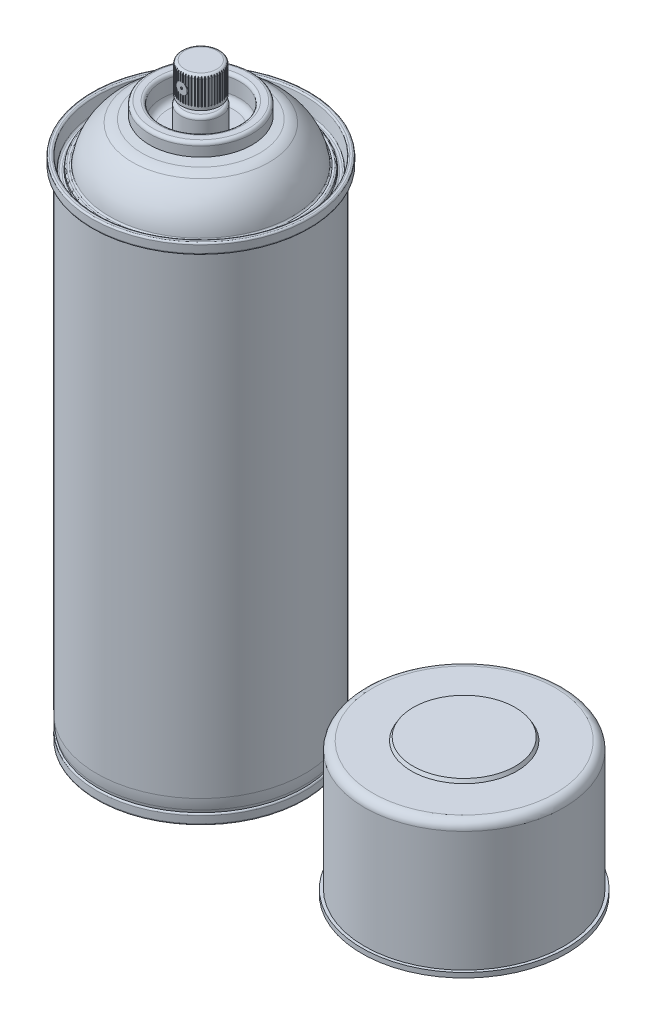
SolidWorks part; units mm, degrees
ref_plane "Front Plane" through (0, 0, 0) normal (0, 0, 1) x (1, 0, 0)
ref_plane "Top Plane" through (0, 0, 0) normal (0, 1, 0) x (1, 0, 0)
ref_plane "Right Plane" through (0, 0, 0) normal (1, 0, 0) x (0, 0, -1)
sketch "Sketch1" plane through (0, 0, 0) normal (0, 1, 0) x (1, 0, 0)
  circle A0 centre (0, 0) radius 32.5
  dimension "D1" = 65
extrude "Boss-Extrude1" add sketch "Sketch1" along normal blind 158
sketch "Sketch2" plane through (0, 0, 0) normal (0, -1, 0) x (1, 0, 0)
  circle A1 centre (0, 0) radius 32.5
  circle A2 centre (0, 0) radius 32.5
  dimension "D1" = 0
chamfer "Chamfer1" distance 1 angle 80 1 edges at (0, 0, 32.5) first distance on face at (0, 0, 32.5)
fillet "Fillet1" radius 19 1 edges at (0, 5.6713, 32.5)
other "Move Face1" flip direction yes face at (0, 0, 31.5) offset 2.5 parameters "D1"=2.5
dome "Dome1" faces to dome 1 distance 6 reverse direction yes elliptical dome no face at (0, 2.5, 31.9408) parameters "D1"=6
extrude "Extrude-Thin1" add sketch "Sketch2" against normal blind 3.2 separate body thin thin type one direction reverse wall 1.5
combine bodies "Combine1" operation type add bodies to combine 101 103
fillet "Fillet2" radius 0.5 4 edges at (31, 0, 0) (0, 3.2, -32.5) (0, 0, -32.5) (0, 2.8602, -31)
sketch "Sketch3" plane through (0, 158, 0) normal (0, 1, 0) x (1, 0, 0)
  circle A1 centre (0, 0) radius 32.5
  circle A2 centre (0, 0) radius 32.5
  dimension "D1" = 0
extrude "Cut-Extrude1" cut sketch "Sketch3" against normal blind 3.9
sketch "Sketch4" plane through (0, 0, 0) normal (0, 0, 1) x (1, 0, 0)
  line L0 (0, 146.9302) -> (0, 222.3926) construction
  line L1 (-12.8, 168.6) -> (-19.8, 167.9876)
  line L2 (0, 158.6) -> (-34, 158.6) construction
  line L3 (0, 173.1) -> (-44.1761, 173.1) construction
  line L4 (-34, 158.6) -> (-32.5, 158.6)
  line L5 (-34, 158.6) -> (-34, 155.3)
  line L6 (-34, 155.3) -> (-32.5, 155.3)
  line L7 (-32.5, 155.3) -> (-32.5, 153.1)
  line L8 (-16, 173.1) -> (-16, 220.9613) construction
  line L9 (-12.2, 170.1) -> (-12.2, 172.1)
  line L10 (-13.2, 173.1) -> (-15, 173.1)
  line L11 (-16, 172.1) -> (-16, 169.1)
  line L12 (-6.25, 165.6) -> (-10.2, 165.6)
  line L13 (-6.25, 165.6) -> (-6.25, 172.1)
  line L14 (-16, 169.1) -> (-15.5, 169.1)
  line L15 (-15.5, 169.1) -> (-15.5, 171.6)
  line L16 (-14.5, 172.6) -> (-13.8, 172.6)
  line L17 (-12.2, 170.1) -> (-12.2, 167.6)
  line L18 (-12.8, 171.6) -> (-12.8, 168.6)
  line L19 (-5.25, 173.1) -> (0, 173.1)
  line L20 (-30.2065, 154.1) -> (-31.7065, 154.1)
  line L21 (-31.7065, 154.1) -> (-32.5, 158.6)
  line L22 (-32.5, 153.1) -> (0, 153.1)
  line L23 (0, 153.1) -> (0, 173.1)
  line L24 (32.5, 154.1) -> (-32.5, 154.1) construction
  line L26 (-30.2065, 154.1) -> (-30.0753, 155.6)
  line L27 (-30.0753, 155.6) -> (-28.5753, 155.6)
  arc A0 (-28.5753, 155.6) -> (-19.8, 167.9876) centre (-12.6943, 153.652) cw
  arc A1 (-15, 173.1) -> (-16, 172.1) centre (-15, 172.1) ccw
  arc A2 (-12.2, 172.1) -> (-13.2, 173.1) centre (-13.2, 172.1) ccw
  arc A3 (-12.8, 171.6) -> (-13.8, 172.6) centre (-13.8, 171.6) ccw
  arc A4 (-15.5, 171.6) -> (-14.5, 172.6) centre (-14.5, 171.6) cw
  arc A5 (-6.25, 172.1) -> (-5.25, 173.1) centre (-5.25, 172.1) cw
  arc A6 (-10.2, 165.6) -> (-12.2, 167.6) centre (-10.2, 167.6) cw
  point P35 (-12.2, 173.1)
  point P38 (-12.8, 172.6)
  point P43 (-6.25, 173.1)
  dimension "D15" = 95
  dimension "D20" = 1
  dimension "D21" = 1
  dimension "D22" = 2
  dimension "D27" = 95
  dimension "D29" = 16
  dimension "D2" = 3.3
  dimension "D3" = 1.5
  dimension "D4" = 14.5
  dimension "D5" = 16
  dimension "D6" = 4
  dimension "D7" = 3
  dimension "D8" = 3.8
  dimension "D9" = 7.5
  dimension "D10" = 6.25
  dimension "D11" = 0.5
  dimension "D12" = 0.5
  dimension "D13" = 4
  dimension "D14" = 0.6
  dimension "D16" = 1.5
  dimension "D17" = 100
  dimension "D18" = 1.5
  dimension "D19" = 20
  dimension "D23" = 34
  dimension "D24" = 1.2
  dimension "D25" = 1.5
  dimension "D26" = 1.5
  dimension "D28" = 7
revolve "Revolve1" add sketch "Sketch4" angle 360 about L0
fillet "Fillet4" radius 0.5 4 edges at (0, 154.1, -31.7065) (0, 158.6, -32.5) (0, 155.3, -34) (0, 158.6, -34)
fillet "Fillet6" radius 0.5 3 edges at (0, 155.6, -28.5753) (0, 155.6, -30.0753) (0, 154.1, -30.2065)
fillet "Fillet7" radius 6.5 1 edges at (0, 167.9876, -19.8)
sketch "Sketch5" plane through (0, 0, 0) normal (0, 0, 1) x (1, 0, 0)
  line L0 (-30.5, 157.1) -> (-30.5, 196.1)
  line L1 (-28.5, 198.1) -> (0, 198.1)
  line L2 (5.25, 173.1) -> (-5.25, 173.1) construction
  line L3 (0, 172.1) -> (0, 198.1) construction
  line L4 (16, 172.1) -> (-16, 172.1) construction
  line L5 (-32, 157.1) -> (-30.5, 157.1)
  line L6 (-31.1, 158.6) -> (-31.1, 196.1)
  line L7 (-28.5, 198.7) -> (-16.5, 198.7)
  line L8 (0, 199.7) -> (0, 198.1)
  line L9 (-31.1, 158.6) -> (-32, 158.6)
  line L10 (-32, 158.6) -> (-32, 157.1)
  line L11 (-16.5, 198.7) -> (-15.9226, 199.7)
  line L12 (-15.9226, 199.7) -> (0, 199.7)
  line L13 (-31.1, 157.1) -> (-31.1, 196.1) construction
  line L14 (-28.5, 198.7) -> (0, 198.7) construction
  arc A1 (-30.5, 196.1) -> (-28.5, 198.1) centre (-28.5, 196.1) cw
  arc A2 (-31.1, 196.1) -> (-28.5, 198.7) centre (-28.5, 196.1) cw
  point P13 (-30.5, 198.1)
  dimension "D3" = 2
  dimension "D1" = 16
  dimension "D2" = 41
  dimension "D5" = 1.5
  dimension "D6" = 1.5
  dimension "D7" = 30.5
  dimension "D8" = 16.5
  dimension "D9" = 1
  dimension "D10" = 120
  dimension "D4" = 0.6
revolve "Revolve2" add sketch "Sketch5" angle 360 about L3
sketch "Sketch6" plane through (0, 0, 0) normal (0, 0, 1) x (1, 0, 0)
  line L0 (0, 172.1) -> (0, 184.1)
  line L1 (0, 172.1) -> (0, 198.1) construction
  line L2 (0, 184.1) -> (-6, 184.1)
  line L3 (-6, 184.1) -> (-6, 174.6)
  line L4 (-6, 174.6) -> (-3, 174.6)
  line L5 (-3, 174.6) -> (-3, 172.1)
  line L6 (16, 172.1) -> (-16, 172.1) construction
  line L7 (-3, 172.1) -> (0, 172.1)
  line L8 (0, 172.1) -> (-0.2637, 172.0477)
  dimension "D1" = 12
  dimension "D2" = 6
  dimension "D3" = 3
  dimension "D4" = 2.5
revolve "Revolve3" add sketch "Sketch6" angle 360 about L0
fillet "Fillet8" radius 1 1 edges at (0, 184.1, -6)
sketch "Sketch7" plane through (0, 0, 0) normal (0, 0, 1) x (1, 0, 0)
  line L0 (0, 172.1) -> (0, 198.1) construction
  circle A0 centre (0, 179.4204) radius 0.3475
extrude "Cut-Extrude2" cut sketch "Sketch7" along normal blind 12.9
sketch "Sketch8" plane through (0, 0, 0) normal (0, 0, 1) x (1, 0, 0)
  circle A0 centre (0, 179.4204) radius 1.75
  circle A1 centre (0, 179.4204) radius 0.3475 construction
  circle A2 centre (0, 179.4204) radius 0.3475
  dimension "D1" = 3.5
extrude "Boss-Extrude2" add sketch "Sketch8" along normal blind 6 separate body
sketch "Sketch9" plane through (0, 184.1, 0) normal (0, 1, 0) x (1, 0, 0)
  line L0 (7, 0) -> (5.5, 0) construction
  line L1 (5.8623, -0.0966) -> (7, -0.4)
  line L2 (7, -0.4) -> (7, 0.4)
  line L3 (7, 0.4) -> (5.8623, 0.0966)
  line L4 (5.5, 0) -> (0, 0) construction
  arc A0 (5.8623, 0.0966) -> (5.8623, -0.0966) centre (5.8881, 0) ccw
  point P3 (7, 0)
  dimension "D4" = 0.1
  dimension "D1" = 5.5
  dimension "D2" = 0.8
  dimension "D3" = 1.5
extrude "Cut-Extrude3" cut sketch "Sketch9" against normal blind 8.5
pattern_circular "CirPattern1" count 50 over 360 of "Cut-Extrude3"
move or copy body "Body-Move/Copy1" bodies to move or copy 107 copy no translate (82.2396, -157.5411, 0)
